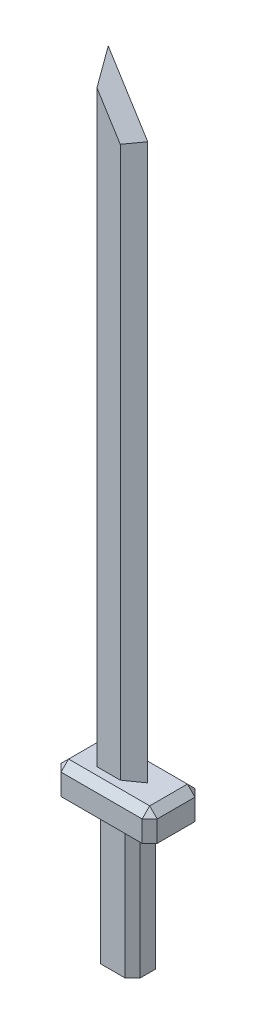
SolidWorks part; units mm, degrees
ref_plane "Front" through (0, 0, 0) normal (0, 0, 1) x (1, 0, 0)
ref_plane "Top" through (0, 0, 0) normal (0, 1, 0) x (1, 0, 0)
ref_plane "Right" through (0, 0, 0) normal (1, 0, 0) x (0, 0, -1)
sketch "Sketch1" plane through (0, 0, 0) normal (0, 0, 1) x (1, 0, 0)
  line L0 (0, 0) -> (0, 81.9424)
  line L1 (0, 81.9424) -> (5.2315, 73.5727)
  line L2 (5.2315, 73.5727) -> (5.2315, 0)
  line L3 (5.2315, 0) -> (0, 0)
  line L4 (-3.7582, 0) -> (8.9897, 0)
  line L5 (-3.7582, 0) -> (-3.7582, -3.8065)
  line L6 (-3.7582, -3.8065) -> (8.9897, -3.8065)
  line L7 (8.9897, 0) -> (8.9897, -3.8065)
  line L8 (2.6157, -21.8812) -> (2.6157, 0) construction
  line L9 (0, -3.8065) -> (5.2315, -3.8065)
  line L10 (0, -3.8065) -> (0, -21.8812)
  line L11 (0, -21.8812) -> (5.2315, -21.8812)
  line L12 (5.2315, -3.8065) -> (5.2315, -21.8812)
  point P8 (2.6157, 0)
  point P16 (4.4788, -21.8812)
  point P17 (0, -3.8065)
  point P18 (0, 0)
  point P19 (0, 0)
  point P20 (0, 0)
extrude "Boss-Extrude1" add sketch "Sketch1" along normal mid plane 3 contours L3 L2 L1 L0 L4 region at (2.5688, 38.9163, 0)
extrude "Boss-Extrude2" add sketch "Sketch1<3>" along normal mid plane 4 separate body contours L12 L11 L10 L9
sketch "Sketch1<3>" plane through (0, 0, 0) normal (0, 0, 1) x (1, 0, 0) same geometry as "Sketch1"
extrude "Boss-Extrude3" add sketch "Sketch1<4>" along normal mid plane 7 contours L6 L7 L4 L5
sketch "Sketch1<4>" plane through (0, 0, 0) normal (0, 0, 1) x (1, 0, 0) same geometry as "Sketch1"
chamfer "Chamfer1" distance 1 angle 45 12 edges at (8.9897, 0, 0) (8.9897, -1.9033, 3.5) (2.6157, 0, 3.5) (8.9897, -1.9033, -3.5) (2.6157, 0, -3.5) (-3.7582, -1.9033, -3.5) (-3.7582, 0, 0) (-3.7582, -1.9033, 3.5) (5.2315, -12.8438, -2) (0, -12.8438, -2) (5.2315, -12.8438, 2) (0, -12.8438, 2)
chamfer "Chamfer2" distance 1.5 angle 55 4 edges at (5.2315, 36.7864, 1.5) (5.2315, 36.7864, -1.5) (2.6157, 77.7576, 1.5) (2.6157, 77.7576, -1.5) first distance on face at (5.2315, 36.7864, 0) first distance on face at (2.6157, 77.7576, 0)
